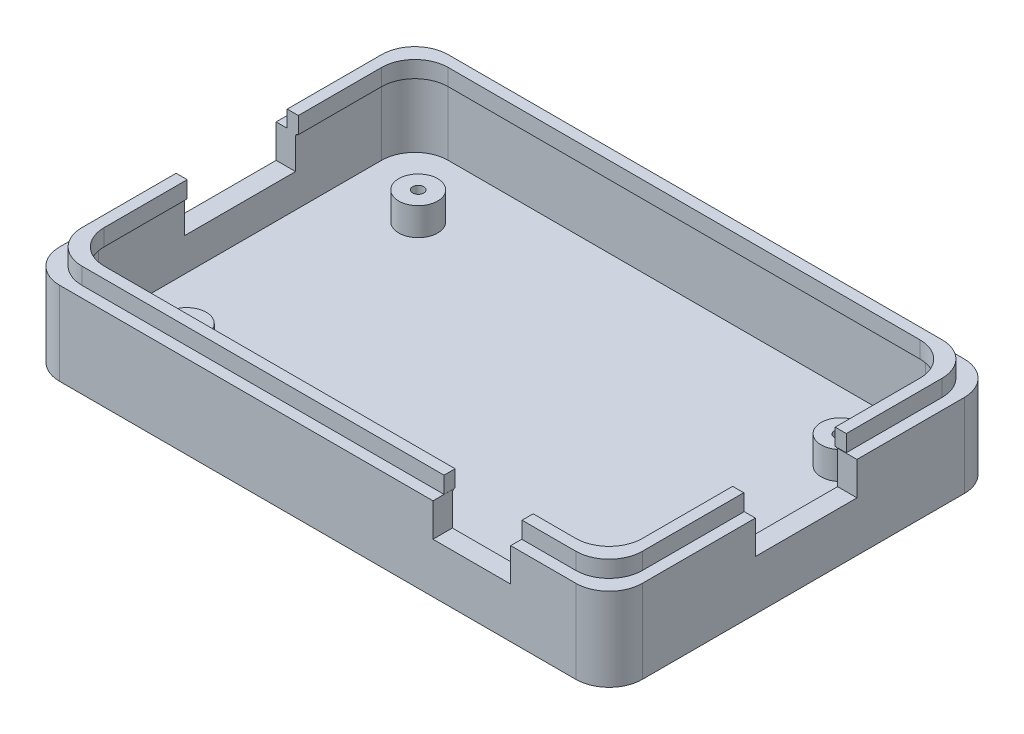
SolidWorks part; units mm, degrees
ref_plane "Front Plane" through (0, 0, 0) normal (0, 0, 1) x (1, 0, 0)
ref_plane "Top Plane" through (0, 0, 0) normal (0, 1, 0) x (1, 0, 0)
ref_plane "Right Plane" through (0, 0, 0) normal (1, 0, 0) x (0, 0, -1)
sketch "Sketch1" plane through (0, 0, 0) normal (0, 1, 0) x (1, 0, 0)
  line L1 (-52.5, 35) -> (52.5, 35)
  line L2 (-52.5, 35) -> (-52.5, -35)
  line L3 (-52.5, -35) -> (52.5, -35)
  line L4 (52.5, 35) -> (52.5, -35)
  line L5 (-52.5, 35) -> (52.5, -35) construction
  line L6 (-52.5, -35) -> (52.5, 35) construction
  point P0 (0, 0)
  dimension "D1" = 105
  dimension "D2" = 70
extrude "Boss-Extrude1" add sketch "Sketch1" along normal blind 15
sketch "Sketch3" plane through (0, 15, 0) normal (0, 1, 0) x (1, 0, 0)
  line L0 (52.5, -35) -> (52.5, 35) construction
  line L1 (49, -31.5) -> (-49, -31.5)
  line L2 (49, -31.5) -> (49, 31.5)
  line L3 (49, 31.5) -> (-49, 31.5)
  line L4 (-49, -31.5) -> (-49, 31.5)
  line L5 (49, -31.5) -> (-49, 31.5) construction
  line L6 (49, 31.5) -> (-49, -31.5) construction
  line L7 (-52.5, -35) -> (52.5, -35) construction
  point P0 (0, 0)
  dimension "D1" = 3.5
  dimension "D2" = 3.5
extrude "Cut-Extrude1" cut sketch "Sketch3" against normal blind 12
fillet "Fillet1" radius 6 8 edges at (-52.5, 7.5, -35) (-52.5, 7.5, 35) (52.5, 7.5, -35) (52.5, 7.5, 35) (49, 9, -31.5) (-49, 9, -31.5) (-49, 9, 31.5) (49, 9, 31.5)
sketch "Sketch4" plane through (0, 3, 0) normal (0, 1, 0) x (1, 0, 0)
  line L0 (-43, -31.5) -> (43, -31.5) construction
  line L1 (49, -25.5) -> (49, 25.5) construction
  circle A0 centre (40, -22.5) radius 3.5
  circle A1 centre (40, 19.2) radius 3.5
  circle A2 centre (-36.1, -22.5) radius 3.5
  circle A3 centre (-36.1, 19.2) radius 3.5
  dimension "D5" = 7
  dimension "D6" = 76.1
  dimension "D1" = 41.7
  dimension "D2" = 9
  dimension "D3" = 76.1
  dimension "D4" = 9
  dimension "D7" = 41.7
extrude "Boss-Extrude2" add sketch "Sketch4" along normal blind 5
sketch "Sketch5" plane through (0, 8, 0) normal (0, 1, 0) x (1, 0, 0)
  circle A0 centre (-36.1, 19.2) radius 1
  circle A1 centre (-36.1, -22.5) radius 1
  circle A2 centre (40, -22.5) radius 1
  circle A3 centre (40, 19.0603) radius 1
  dimension "D1" = 2
extrude "Cut-Extrude2" cut sketch "Sketch5" against normal blind 8
sketch "Sketch6" plane through (0, 15, 0) normal (0, 1, 0) x (1, 0, 0)
  line L0 (49, -25.5) -> (49, 25.5) construction
  line L1 (49, 9.66) -> (52.5, 9.66)
  line L2 (49, 9.66) -> (49, -8.64)
  line L3 (49, -8.64) -> (52.5, -8.64)
  line L4 (52.5, 9.66) -> (52.5, -8.64)
  line L5 (52.5, -29) -> (52.5, 29) construction
  line L6 (-46.5, -35) -> (46.5, -35) construction
  line L7 (34.76, -35) -> (20.76, -35)
  line L8 (34.76, -35) -> (34.76, -31.5)
  line L9 (34.76, -31.5) -> (20.76, -31.5)
  line L10 (20.76, -35) -> (20.76, -31.5)
  line L11 (-43, -31.5) -> (43, -31.5) construction
  line L12 (-52.5, 29) -> (-52.5, -29) construction
  line L13 (-52.5, 10) -> (-49, 10)
  line L14 (-52.5, 10) -> (-52.5, -10)
  line L15 (-52.5, -10) -> (-49, -10)
  line L16 (-49, 10) -> (-49, -10)
  line L17 (-49, 25.5) -> (-49, -25.5) construction
  dimension "D1" = 14
  dimension "D2" = 20
  dimension "D3" = 25
  dimension "D4" = 14.24
  dimension "D5" = 22.86
  dimension "D6" = 18.3
extrude "Cut-Extrude3" cut sketch "Sketch6" against normal blind 6
sketch "Sketch7" plane through (0, 15, 0) normal (0, 1, 0) x (1, 0, 0)
  line L0 (0, 35) -> (0, -35) construction
  line L1 (46.5, 35) -> (-46.5, 35) construction
  line L2 (-46.5, -35) -> (20.76, -35) construction
  line L3 (-52.5, -10) -> (-52.5, -29) construction
  line L4 (-44.5, 33) -> (44.5, 33)
  line L5 (-50.5, 27) -> (-50.5, 10)
  line L6 (-44.5, -33) -> (20.7545, -33)
  line L7 (50.5, 27) -> (50.5, 9.7366)
  line L8 (-50.5, 33) -> (50.5, -33) construction
  line L9 (-50.5, -33) -> (50.5, 33) construction
  line L10 (50.5, -8.7396) -> (50.5, -27)
  line L11 (-42.5, 31) -> (42.5, 31)
  line L12 (-48.5, 25) -> (-48.5, 10)
  line L13 (-42.5, -31) -> (20.7545, -31)
  line L14 (48.5, 25) -> (48.5, 9.7366)
  line L15 (-48.5, 31) -> (48.5, -31) construction
  line L16 (-48.5, -31) -> (48.5, 31) construction
  line L17 (50.5, 9.7366) -> (48.5, 9.7366)
  line L19 (50.5, -8.7396) -> (48.5, -8.7396)
  line L20 (-50.5, 10) -> (-48.5, 10)
  line L21 (48.5, -8.7396) -> (48.5, -25)
  line L22 (34.8092, -31) -> (42.5, -31)
  line L23 (-50.5, -10.027) -> (-48.5, -10.027)
  line L25 (-48.5, -10.027) -> (-48.5, -25)
  line L26 (-50.5, -10.027) -> (-50.5, -27)
  line L27 (34.8092, -33) -> (34.8092, -31)
  line L29 (20.7545, -33) -> (20.7545, -31)
  line L30 (34.8092, -33) -> (44.5, -33)
  arc A0 (44.5, 33) -> (50.5, 27) centre (44.5, 27) cw
  arc A1 (-44.5, 33) -> (-50.5, 27) centre (-44.5, 27) ccw
  arc A2 (44.5, -33) -> (50.5, -27) centre (44.5, -27) ccw
  arc A3 (-50.5, -27) -> (-44.5, -33) centre (-44.5, -27) ccw
  arc A4 (-42.5, 31) -> (-48.5, 25) centre (-42.5, 25) ccw
  arc A5 (-48.5, -25) -> (-42.5, -31) centre (-42.5, -25) ccw
  arc A6 (42.5, -31) -> (48.5, -25) centre (42.5, -25) ccw
  arc A7 (42.5, 31) -> (48.5, 25) centre (42.5, 25) cw
  point P7 (0, 0)
  point P26 (0, 0)
  dimension "D3" = 6
  dimension "D6" = 6
  dimension "D1" = 2
  dimension "D2" = 2
  dimension "D4" = 2
  dimension "D5" = 2
extrude "Boss-Extrude3" add sketch "Sketch7" along normal blind 3
fillet "Fillet2" radius 0.5 11 edges at (49, 15, 17.1198) (47.2426, 15, 29.7426) (-49, 15, 17.7635) (-47.2426, 15, 29.7426) (49, 15, -17.6183) (47.2426, 15, -29.7426) (-49, 15, -17.75) (-47.2426, 15, -29.7426) (38.9046, 15, 31.5) (-11.1228, 15, 31.5) (0, 15, -31.5)
equation "\"D2@Sketch3\"=\"D1@Sketch3\""
equation "\"D4@Sketch4\"=\"D2@Sketch4\""
equation "\"D6@Sketch4\"=\"D3@Sketch4\""
equation "\"D7@Sketch4\"=\"D1@Sketch4\""
